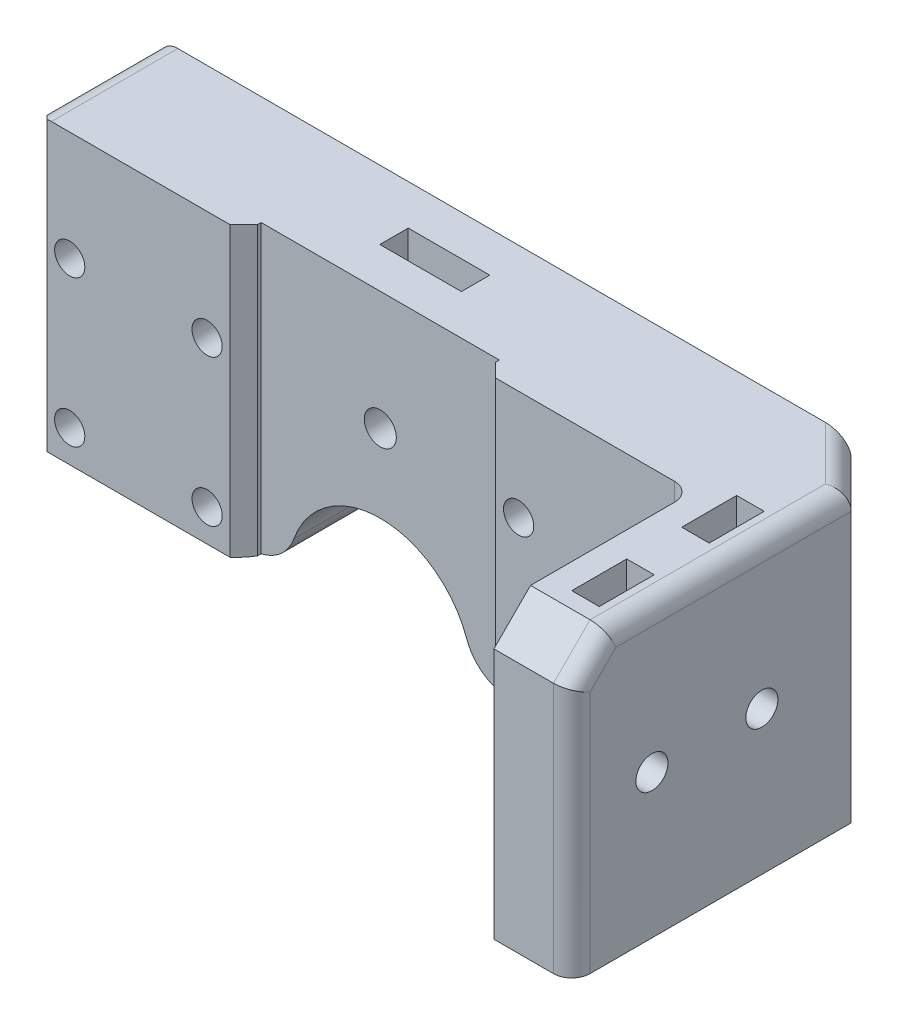
SolidWorks part; units mm, degrees
ref_plane "Alzado" through (0, 0, 0) normal (0, 0, 1) x (1, 0, 0)
ref_plane "Planta" through (0, 0, 0) normal (0, 1, 0) x (1, 0, 0)
ref_plane "Vista lateral" through (0, 0, 0) normal (1, 0, 0) x (0, 0, -1)
sketch "Croquis1" plane through (0, 0, 0) normal (0, 1, 0) x (1, 0, 0)
  line L1 (0, 0) -> (72, 0)
  line L2 (0, 0) -> (0, 35.8)
  line L3 (0, 35.8) -> (72, 35.8)
  line L4 (72, 0) -> (72, 35.8)
  dimension "D1" = 72
  dimension "D2" = 35.8
extrude "Saliente-Extruir1" add sketch "Croquis1" along normal blind 23
sketch "Croquis2" plane through (0, 0, -35.8) normal (0, 0, -1) x (-1, 0, 0)
  line L0 (-36, 23) -> (-36, 0) construction
  line L1 (-72, 23) -> (0, 23) construction
  line L2 (-72, 0) -> (0, 0) construction
  line L3 (-69.4, 20) -> (-47, 20)
  line L4 (-69.4, 20) -> (-69.4, -5)
  line L5 (-2.6, 20) -> (-2.6, -5)
  line L6 (-2.6, -5) -> (-69.4, -5)
  line L7 (-25, 20) -> (-2.6, 20)
  line L8 (-47, 23) -> (-25, 23)
  line L9 (-47, 23) -> (-47, 20)
  line L11 (-25, 23) -> (-25, 20)
  point P16 (-36, 23)
  dimension "D1" = 3
  dimension "D2" = 66.8
  dimension "D3" = 25
  dimension "D4" = 22
  dimension "D5" = 22.4
extrude "Cortar-Extruir2" cut sketch "Croquis2" against normal blind 2.8
sketch "Croquis3" plane through (0, 23, 0) normal (0, 1, 0) x (1, 0, 0)
  line L0 (36, 33) -> (36, 0) construction
  line L1 (25, 33) -> (47, 33) construction
  line L2 (0, 0) -> (72, 0) construction
  line L4 (33.05, 31.4) -> (38.95, 31.4)
  line L5 (33.05, 31.4) -> (33.05, 28.3)
  line L6 (33.05, 28.3) -> (38.95, 28.3)
  line L7 (38.95, 31.4) -> (38.95, 28.3)
  point P10 (36, 28.3)
  dimension "D1" = 4.4
  dimension "D2" = 3.1
  dimension "D3" = 5.9
extrude "Cortar-Extruir3" cut sketch "Croquis3" against normal blind 7.91
sketch "Croquis4" plane through (0, 0, -28.3) normal (0, 0, -1) x (-1, 0, 0)
  line L0 (-36, 23) -> (-36, 15.09) construction
  line L1 (-33.05, 23) -> (-38.95, 23) construction
  line L2 (-33.05, 15.09) -> (-38.95, 15.09) construction
  line L3 (-38.95, 16.7932) -> (-38.95, 15.09)
  line L4 (-36, 15.09) -> (-33.05, 16.7932)
  line L5 (-33.05, 16.7932) -> (-33.05, 20.1995) construction
  line L6 (-33.05, 20.1995) -> (-36, 21.9027) construction
  line L7 (-36, 21.9027) -> (-38.95, 20.1995) construction
  line L8 (-38.95, 20.1995) -> (-38.95, 16.7932) construction
  line L9 (-38.95, 16.7932) -> (-36, 15.09)
  line L10 (-38.95, 15.09) -> (-36, 15.09)
  line L11 (-36, 15.09) -> (-33.05, 15.09)
  line L12 (-33.05, 15.09) -> (-33.05, 16.7932)
  circle A0 centre (-36, 18.4964) radius 2.95 construction
  line M6 (-38.95, 23) -> (-38.95, 15.09)
  line M7 (-38.95, 15.09) -> (-33.05, 15.09)
  line M8 (-33.05, 15.09) -> (-33.05, 23)
extrude "Saliente-Extruir3" add sketch "Croquis4" along normal up to surface (3.1 mm away) contours L4 M7 M8 | L9 M6 M7 region at (37.9667, 15.6577, -28.3) region at (34.0333, 15.6577, -28.3) up to face at (36, 19.045, -31.4)
sketch "Croquis7" plane through (0, 23, 0) normal (0, 1, 0) x (1, 0, 0)
  line L0 (72, 0) -> (72, 35.8) construction
  line L1 (0, 0) -> (72, 0)
  line L2 (0, 0) -> (0, 22)
  line L3 (0, 22) -> (72, 22)
  line L4 (72, 0) -> (72, 22)
  dimension "D1" = 22
extrude "Cortar-Extruir6" cut sketch "Croquis7" against normal blind 37.91
sketch "Croquis9" plane through (0, 0, -28.3) normal (0, 0, -1) x (-1, 0, 0)
  line L0 (-36, 23) -> (-36, 15.09) construction
  line L1 (-33.05, 23) -> (-38.95, 23) construction
  line L2 (-33.05, 16.7932) -> (-33.05, 23) construction
  line L3 (-36, 15.09) -> (-33.05, 16.7932) construction
  line L4 (-33.05, 16.7932) -> (-33.05, 20.1995) construction
  line L5 (-33.05, 20.1995) -> (-36, 21.9027) construction
  line L6 (-36, 21.9027) -> (-38.95, 20.1995) construction
  line L7 (-38.95, 20.1995) -> (-38.95, 16.7932) construction
  line L8 (-38.95, 16.7932) -> (-36, 15.09) construction
  circle A0 centre (-36, 18.4964) radius 2.95 construction
  circle A1 centre (-36, 18.4964) radius 1.75
  dimension "D1" = 3.5
extrude "Cortar-Extruir8" cut sketch "Croquis9" against normal blind 15 and the other way blind 15
sketch "Croquis11" plane through (0, 23, 0) normal (0, 1, 0) x (1, 0, 0)
  line L1 (72, 35.8) -> (80.5, 35.8)
  line L2 (72, 35.8) -> (72, 0.3)
  line L3 (72, 0.3) -> (80.5, 0.3)
  line L4 (80.5, 35.8) -> (80.5, 0.3)
  dimension "D1" = 35.5
  dimension "D2" = 8.5
extrude "Saliente-Extruir4" add sketch "Croquis11" against normal up to surface (23 mm away) up to face at (36, 0, -31.65)
sketch "Croquis12" plane through (0, 23, 0) normal (0, 1, 0) x (1, 0, 0)
  line L0 (76.25, 0.3) -> (76.25, 35.8) construction
  line L1 (72, 0.3) -> (80.5, 0.3) construction
  line L2 (80.5, 35.8) -> (47, 35.8) construction
  line L4 (74.75, 24.05) -> (77.75, 24.05)
  line L5 (74.75, 24.05) -> (74.75, 18.05)
  line L6 (74.75, 18.05) -> (77.75, 18.05)
  line L7 (77.75, 24.05) -> (77.75, 18.05)
  line L8 (74.75, 12.05) -> (77.75, 12.05)
  line L9 (74.75, 12.05) -> (74.75, 6.05)
  line L10 (74.75, 6.05) -> (77.75, 6.05)
  line L11 (77.75, 12.05) -> (77.75, 6.05)
  point P10 (76.25, 24.05)
  point P15 (76.25, 12.05)
  point P17 (77.75, 9.05)
  dimension "D1" = 6
  dimension "D2" = 18
  dimension "D3" = 11.75
  dimension "D4" = 3
  dimension "D5" = 8.75
extrude "Cortar-Extruir11" cut sketch "Croquis12" against normal blind 10.79
chamfer "Chaflán3" distance 5 angle 45 1 edges at (80.5, 11.5, -35.8)
sketch "Croquis17" plane through (0, 0, -33) normal (0, 0, -1) x (-1, 0, 0)
  line L0 (-36, 23) -> (-36, 0) construction
  line L1 (-25, 23) -> (-47, 23) construction
  line L2 (-69.4, 0) -> (-2.6, 0) construction
  circle A0 centre (-36, 0) radius 10
  dimension "D1" = 20
extrude "Cortar-Extruir14" cut sketch "Croquis17" against normal blind 30.5
sketch "Croquis18" plane through (0, 23, 0) normal (0, 1, 0) x (1, 0, 0)
  line L11 (0, 35.8) -> (75.5, 35.8)
  line L20 (33.05, 28.3) -> (38.95, 28.3)
  line L21 (33.05, 31.4) -> (33.05, 28.3)
  line L22 (80.5, 0.3) -> (80.5, 30.8)
  line L23 (80.5, 30.8) -> (75.5, 35.8)
  line L24 (75.5, 35.8) -> (47, 35.8)
  line L25 (47, 35.8) -> (47, 33)
  line L26 (47, 33) -> (25, 33)
  line L27 (25, 33) -> (25, 35.8)
  line L28 (25, 35.8) -> (0, 35.8)
  line L29 (0, 35.8) -> (0, 22)
  line L30 (0, 22) -> (72, 22)
  line L31 (72, 22) -> (72, 0.3)
  line L32 (72, 0.3) -> (80.5, 0.3)
  line L33 (80.5, 0.3) -> (80.5, 30.8)
  line L34 (80.5, 30.8) -> (75.5, 35.8)
  line L35 (38.95, 28.3) -> (38.95, 31.4)
  line L36 (38.95, 31.4) -> (33.05, 31.4)
  line L37 (33.05, 28.3) -> (38.95, 28.3)
  line L38 (33.05, 31.4) -> (33.05, 28.3)
  line L39 (38.95, 28.3) -> (38.95, 31.4)
  line L40 (0, 35.8) -> (0, 22)
  line L41 (0, 22) -> (72, 22)
  line L42 (72, 22) -> (72, 0.3)
  line L43 (72, 0.3) -> (80.5, 0.3)
  line L44 (38.95, 31.4) -> (33.05, 31.4)
  line L53 (77.75, 24.05) -> (74.75, 24.05)
  line L54 (74.75, 18.05) -> (77.75, 18.05)
  line L55 (77.75, 18.05) -> (77.75, 24.05)
  line L56 (74.75, 24.05) -> (74.75, 18.05)
  line L57 (77.75, 24.05) -> (74.75, 24.05)
  line L58 (74.75, 18.05) -> (77.75, 18.05)
  line L59 (77.75, 18.05) -> (77.75, 24.05)
  line L60 (74.75, 24.05) -> (74.75, 18.05)
  line L65 (74.75, 6.05) -> (77.75, 6.05)
  line L66 (77.75, 6.05) -> (77.75, 12.05)
  line L67 (74.75, 12.05) -> (74.75, 6.05)
  line L68 (77.75, 12.05) -> (74.75, 12.05)
  line L69 (74.75, 6.05) -> (77.75, 6.05)
  line L70 (77.75, 6.05) -> (77.75, 12.05)
  line L71 (74.75, 12.05) -> (74.75, 6.05)
  line L72 (77.75, 12.05) -> (74.75, 12.05)
  dimension "D1" = 0
  dimension "D2" = 0
  dimension "D3" = 0
  dimension "D4" = 0
extrude "Saliente-Extruir5" add sketch "Croquis18" along normal blind 3.5
sketch "Croquis19" plane through (0, 26.5, 0) normal (0, 1, 0) x (1, 0, 0)
  line L0 (36, 28.3) -> (36, 22) construction
  line L1 (33.05, 28.3) -> (38.95, 28.3) construction
  line L2 (0, 22) -> (72, 22) construction
  line L4 (23, 23.9) -> (49, 23.9)
  line L5 (23, 23.9) -> (23, 22)
  line L6 (23, 22) -> (49, 22)
  line L7 (49, 23.9) -> (49, 22)
  point P10 (36, 22)
  dimension "D1" = 1.9
  dimension "D2" = 26
extrude "Cortar-Extruir15" cut sketch "Croquis19" against normal up to surface (26.5 mm away) up to face at (9.5333, 0, -30.2667)
chamfer "Chaflán4" distance 1.5 angle 45 3 edges at (49, 13.25, -22) (0, 13.25, -22) (23, 13.25, -22)
sketch "Croquis20" plane through (0, 0, -22) normal (0, 0, 1) x (1, 0, 0)
  line L0 (36, 26.5) -> (36, 0) construction
  line L1 (4, 3.5) -> (19, 3.5) construction
  line L2 (4, 3.5) -> (4, 19.5) construction
  line L3 (4, 19.5) -> (19, 19.5) construction
  line L4 (19, 3.5) -> (19, 19.5) construction
  line L6 (26, 0) -> (46, 0) construction
  line L7 (49, 26.5) -> (23, 26.5) construction
  circle A0 centre (4, 3.5) radius 1.65
  circle A1 centre (19, 3.5) radius 1.65
  circle A2 centre (4, 19.5) radius 1.65
  circle A3 centre (19, 19.5) radius 1.65
  circle A4 centre (53, 3.5) radius 1.65
  circle A5 centre (68, 3.5) radius 1.65 construction
  circle A6 centre (53, 19.5) radius 1.65
  circle A7 centre (68, 19.5) radius 1.65
  dimension "D3" = 3.3
  dimension "D1" = 3.5
  dimension "D2" = 4
  dimension "D4" = 15
  dimension "D5" = 16
extrude "Cortar-Extruir16" cut sketch "Croquis20" against normal up to surface (13.8 mm away) up to face at (36.5833, 14.9167, -35.8)
sketch "Croquis21" plane through (0, 0, -33) normal (0, 0, -1) x (-1, 0, 0)
  circle A0 centre (-68, 19.5) radius 2.85
  circle A2 centre (-53, 3.5) radius 2.85
  circle A3 centre (-53, 19.5) radius 2.85
  circle A4 centre (-19, 19.5) radius 2.85
  circle A5 centre (-19, 3.5) radius 2.85
  circle A6 centre (-4, 3.5) radius 2.85
  circle A7 centre (-4, 19.5) radius 2.85
  dimension "D1" = 5.7
extrude "Cortar-Extruir17" cut sketch "Croquis21" against normal blind 3 and the other way blind 23.5
sketch "Croquis22" plane through (80.5, 0, 0) normal (1, 0, 0) x (0, 0, -1)
  line L0 (0.3, 15.675) -> (30.8, 15.675) construction
  line L1 (0.3, 0) -> (0.3, 26.5) construction
  line L2 (30.8, 0) -> (30.8, 26.5) construction
  line L3 (15.55, 26.5) -> (15.55, 0) construction
  line L4 (0.3, 26.5) -> (30.8, 26.5) construction
  line L5 (0.3, 0) -> (30.8, 0) construction
  line L6 (21.05, 23.675) -> (21.05, 7.675) construction
  circle A0 centre (21.05, 15.675) radius 1.75
  circle A1 centre (9.05, 15.675) radius 1.75
  point P17 (15.55, 15.675)
  point P20 (21.05, 15.675)
  dimension "D3" = 3.5
  dimension "D1" = 10.825
  dimension "D2" = 5.5
  dimension "D4" = 16
  dimension "D5" = 2.825
  dimension "D6" = 12
extrude "Cortar-Extruir18" cut sketch "Croquis22" against normal up to surface (2.75 mm away) up to face at (77.75, 19.355, -21.05)
fillet "Redondeo3" radius 5 2 edges at (46, 0, -28.45) (26, 0, -28.45)
fillet "Redondeo4" radius 2 1 edges at (72, 13.25, -22)
sketch "Croquis27" plane through (74.75, 0, 0) normal (1, 0, 0) x (0, 0, -1)
  line L0 (9.05, 26.5) -> (9.05, 12.21) construction
  line L1 (12.05, 26.5) -> (6.05, 26.5) construction
  line L2 (12.05, 12.21) -> (6.05, 12.21) construction
  line L3 (12.05, 12.21) -> (12.05, 26.5) construction
  line L4 (9.05, 12.21) -> (12.05, 13.9421)
  line L5 (12.05, 13.9421) -> (12.05, 17.4062)
  line L6 (12.05, 17.4062) -> (9.05, 19.1382)
  line L7 (9.05, 19.1382) -> (6.05, 17.4062)
  line L8 (6.05, 17.4062) -> (6.05, 13.9421)
  line L9 (6.05, 13.9421) -> (9.05, 12.21)
  line L10 (6.05, 13.9421) -> (6.05, 12.21)
  line L11 (9.05, 12.21) -> (6.05, 12.21)
  line L12 (12.05, 12.21) -> (12.05, 13.9421)
  line L13 (12.05, 12.21) -> (18.05, 12.21) construction
  line L14 (15.05, 12.21) -> (15.05, 26.5) construction
  line L15 (20, 26.5) -> (0.3, 26.5) construction
  line L16 (6.05, 12.21) -> (6.05, 13.9421)
  line L17 (12.05, 13.9421) -> (12.05, 12.21)
  line L18 (12.05, 13.9421) -> (9.05, 12.21)
  line L19 (12.05, 17.4062) -> (12.05, 13.9421)
  line L20 (9.05, 19.1382) -> (12.05, 17.4062)
  line L21 (6.05, 17.4062) -> (9.05, 19.1382)
  line L22 (6.05, 13.9421) -> (6.05, 17.4062)
  line L23 (9.05, 12.21) -> (6.05, 13.9421)
  line L24 (9.05, 12.21) -> (12.05, 13.9421)
  line L25 (12.05, 13.9421) -> (12.05, 17.4062)
  line L26 (12.05, 17.4062) -> (9.05, 19.1382)
  line L27 (9.05, 19.1382) -> (6.05, 17.4062)
  line L28 (6.05, 17.4062) -> (6.05, 13.9421)
  line L29 (6.05, 13.9421) -> (9.05, 12.21)
  line L30 (6.05, 13.9421) -> (6.05, 12.21)
  line L31 (12.05, 12.21) -> (12.05, 13.9421)
  line L32 (6.05, 12.21) -> (6.05, 13.9421)
  line L33 (12.05, 13.9421) -> (12.05, 12.21)
  line L34 (12.05, 13.9421) -> (9.05, 12.21)
  line L35 (12.05, 17.4062) -> (12.05, 13.9421)
  line L36 (9.05, 19.1382) -> (12.05, 17.4062)
  line L37 (6.05, 17.4062) -> (9.05, 19.1382)
  line L38 (6.05, 13.9421) -> (6.05, 17.4062)
  line L39 (9.05, 12.21) -> (6.05, 13.9421)
  line L40 (21.05, 26.5) -> (21.05, 12.21) construction
  line L41 (21.05, 12.21) -> (24.05, 13.9421)
  line L42 (24.05, 13.9421) -> (24.05, 17.4062)
  line L43 (24.05, 17.4062) -> (21.05, 19.1382)
  line L44 (21.05, 19.1382) -> (18.05, 17.4062)
  line L45 (18.05, 17.4062) -> (18.05, 13.9421)
  line L46 (18.05, 13.9421) -> (21.05, 12.21)
  line L47 (18.05, 13.9421) -> (18.05, 12.21)
  line L48 (24.05, 12.21) -> (24.05, 13.9421)
  line L49 (18.05, 12.21) -> (18.05, 13.9421)
  line L50 (24.05, 13.9421) -> (24.05, 12.21)
  line L51 (24.05, 13.9421) -> (21.05, 12.21)
  line L52 (24.05, 17.4062) -> (24.05, 13.9421)
  line L53 (21.05, 19.1382) -> (24.05, 17.4062)
  line L54 (18.05, 17.4062) -> (21.05, 19.1382)
  line L55 (18.05, 13.9421) -> (18.05, 17.4062)
  line L56 (21.05, 12.21) -> (18.05, 13.9421)
  line L57 (21.05, 12.21) -> (24.05, 13.9421)
  line L58 (24.05, 13.9421) -> (24.05, 17.4062)
  line L59 (24.05, 17.4062) -> (21.05, 19.1382)
  line L60 (21.05, 19.1382) -> (18.05, 17.4062)
  line L61 (18.05, 17.4062) -> (18.05, 13.9421)
  line L62 (18.05, 13.9421) -> (21.05, 12.21)
  line L63 (18.05, 13.9421) -> (18.05, 12.21)
  line L64 (24.05, 12.21) -> (24.05, 13.9421)
  line L65 (18.05, 12.21) -> (18.05, 13.9421)
  line L66 (24.05, 12.21) -> (18.05, 12.21)
  line L67 (24.05, 13.9421) -> (24.05, 12.21)
  line L68 (24.05, 13.9421) -> (21.05, 12.21)
  line L69 (24.05, 17.4062) -> (24.05, 13.9421)
  line L70 (21.05, 19.1382) -> (24.05, 17.4062)
  line L71 (18.05, 17.4062) -> (21.05, 19.1382)
  line L72 (18.05, 13.9421) -> (18.05, 17.4062)
  line L73 (21.05, 12.21) -> (18.05, 13.9421)
  line L74 (9.05, 12.21) -> (12.05, 12.21)
  circle A0 centre (9.05, 15.6741) radius 3 construction
  circle A1 centre (21.05, 15.6741) radius 3 construction
  line M3 (12.05, 12.21) -> (12.05, 26.5)
  line M5 (6.05, 26.5) -> (6.05, 12.21)
  line M6 (6.05, 12.21) -> (12.05, 12.21)
  dimension "D1" = 6.9282
extrude "Saliente-Extruir6" add sketch "Croquis27" along normal up to surface (3 mm away) contours L9 M5 M6 | L4 M6 M3 | L66 L46 L47 | L66 L48 L41 region at (74.75, 12.7874, -7.05) region at (74.75, 12.7874, -11.05) region at (74.75, 12.7874, -19.05) region at (74.75, 12.7874, -23.05) up to face at (77.75, 15.675, -22.8)
sketch "Croquis29" plane through (0, 26.5, 0) normal (0, 1, 0) x (1, 0, 0)
  line L28 (49, 23.9) -> (49, 23.5)
  line L29 (49, 23.5) -> (50.5, 22)
  line L30 (50.5, 22) -> (70, 22)
  line L31 (72, 20) -> (72, 0.3)
  line L32 (72, 0.3) -> (80.5, 0.3)
  line L33 (80.5, 0.3) -> (80.5, 30.8)
  line L34 (80.5, 30.8) -> (75.5, 35.8)
  line L35 (75.5, 35.8) -> (0, 35.8)
  line L36 (0, 35.8) -> (0, 23.5)
  line L37 (0, 23.5) -> (1.5, 22)
  line L38 (1.5, 22) -> (21.5, 22)
  line L39 (21.5, 22) -> (23, 23.5)
  line L40 (23, 23.5) -> (23, 23.9)
  line L41 (23, 23.9) -> (49, 23.9)
  line L42 (49, 23.9) -> (49, 23.5)
  line L43 (49, 23.5) -> (50.5, 22)
  line L44 (50.5, 22) -> (70, 22)
  line L45 (72, 20) -> (72, 0.3)
  line L46 (72, 0.3) -> (80.5, 0.3)
  line L47 (80.5, 0.3) -> (80.5, 30.8)
  line L48 (80.5, 30.8) -> (75.5, 35.8)
  line L49 (75.5, 35.8) -> (0, 35.8)
  line L50 (0, 35.8) -> (0, 23.5)
  line L51 (0, 23.5) -> (1.5, 22)
  line L52 (1.5, 22) -> (21.5, 22)
  line L53 (21.5, 22) -> (23, 23.5)
  line L54 (23, 23.5) -> (23, 23.9)
  line L55 (23, 23.9) -> (49, 23.9)
  line L158 (38.95, 28.3) -> (38.95, 31.4)
  line L159 (33.05, 31.4) -> (33.05, 28.3)
  line L160 (38.95, 31.4) -> (33.05, 31.4)
  line L161 (33.05, 28.3) -> (38.95, 28.3)
  line L162 (38.95, 28.3) -> (38.95, 31.4)
  line L163 (33.05, 31.4) -> (33.05, 28.3)
  line L164 (38.95, 31.4) -> (33.05, 31.4)
  line L165 (33.05, 28.3) -> (38.95, 28.3)
  line L176 (74.75, 18.05) -> (77.75, 18.05)
  line L177 (77.75, 24.05) -> (74.75, 24.05)
  line L178 (74.75, 24.05) -> (74.75, 18.05)
  line L179 (77.75, 18.05) -> (77.75, 24.05)
  line L180 (74.75, 18.05) -> (77.75, 18.05)
  line L181 (77.75, 24.05) -> (74.75, 24.05)
  line L182 (74.75, 24.05) -> (74.75, 18.05)
  line L183 (77.75, 18.05) -> (77.75, 24.05)
  line L194 (77.75, 6.05) -> (77.75, 12.05)
  line L195 (74.75, 12.05) -> (74.75, 6.05)
  line L196 (77.75, 12.05) -> (74.75, 12.05)
  line L197 (74.75, 6.05) -> (77.75, 6.05)
  line L198 (77.75, 6.05) -> (77.75, 12.05)
  line L199 (74.75, 12.05) -> (74.75, 6.05)
  line L200 (77.75, 12.05) -> (74.75, 12.05)
  line L201 (74.75, 6.05) -> (77.75, 6.05)
  arc A2 (72, 20) -> (70, 22) centre (70, 20) ccw
  arc A3 (72, 20) -> (70, 22) centre (70, 20) ccw
  dimension "D1" = 0
  dimension "D2" = 0
  dimension "D3" = 0
  dimension "D4" = 0
extrude "Saliente-Extruir7" add sketch "Croquis29" along normal blind 4.95
chamfer "Chaflán5" distance 4 angle 45 1 edges at (76.25, 31.45, -0.3)
fillet "Redondeo5" radius 2 5 edges at (78, 31.45, -33.3) (80.5, 13.725, -0.3) (80.5, 29.45, -2.3) (80.5, 31.45, -17.55) (0, 31.45, -29.65)
sketch "Croquis30" plane through (0, 31.45, 0) normal (0, 1, 0) x (1, 0, 0)
  line L0 (38.95, 28.3) -> (36, 28.3) construction
  line L1 (31.55, 31.4) -> (40.45, 31.4)
  line L2 (31.55, 31.4) -> (31.55, 28.3)
  line L3 (31.55, 28.3) -> (40.45, 28.3)
  line L4 (40.45, 31.4) -> (40.45, 28.3)
  line L5 (38.95, 31.4) -> (33.05, 31.4) construction
  point P9 (36, 31.4)
  dimension "D1" = 8.9
extrude "Cortar-Extruir19" cut sketch "Croquis30" against normal blind 6.45
chamfer "Chaflán6" distance 1.5 angle 45 2 edges at (40.45, 25, -29.85) (31.55, 25, -29.85)
